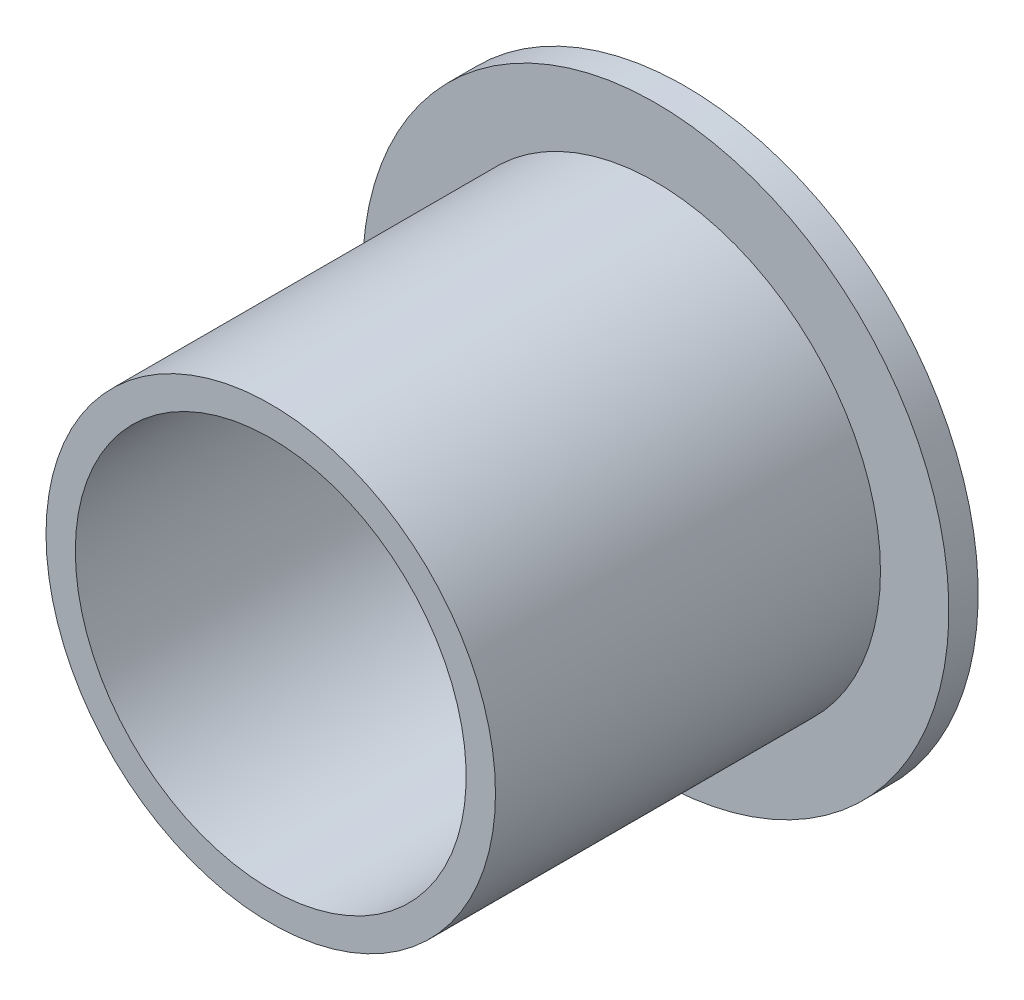
SolidWorks part; units mm, degrees
ref_plane "Front" through (0, 0, 0) normal (0, 0, 1) x (1, 0, 0)
ref_plane "Top" through (0, 0, 0) normal (0, 1, 0) x (1, 0, 0)
ref_plane "Right" through (0, 0, 0) normal (1, 0, 0) x (0, 0, -1)
ref_axis "side-side" through (80.9, 0, 0) along (-1, 0, 0)
ref_axis "up-down" through (0, 50, 0) along (0, -1, 0)
ref_axis "front-back" through (0, 0, -80.9) along (0, 0, 1)
sketch "Sketch1" plane through (0, 0, 0) normal (1, 0, 0) x (0, 0, -1)
  line L0 (0, 0) -> (-73.7719, 0) construction
  line L1 (1.5, 10) -> (-19.7, 10)
  line L2 (1.5, 10) -> (1.5, 15)
  line L3 (1.5, 15) -> (0, 15)
  line L4 (-19.7, 10) -> (-19.7, 11.5)
  line L7 (-19.7, 11.5) -> (0, 11.5)
  line L8 (0, 15) -> (0, 11.5)
  dimension "D1" = 20
  dimension "D2" = 23
  dimension "D3" = 1.5
  dimension "D4" = 30
  dimension "D5" = 21.2
revolve "Revolve1" add sketch "Sketch1" angle 360 about L0
sketch "Sketch2" plane through (0, 0, 0) normal (0, 0, 1) x (1, 0, 0)
  circle A1 centre (0, 0) radius 15
  circle A2 centre (0, 0) radius 15
  dimension "D1" = 0
extrude "Cut-Extrude1" [suppressed] cut sketch "Sketch2" along normal through all from offset 6.35
